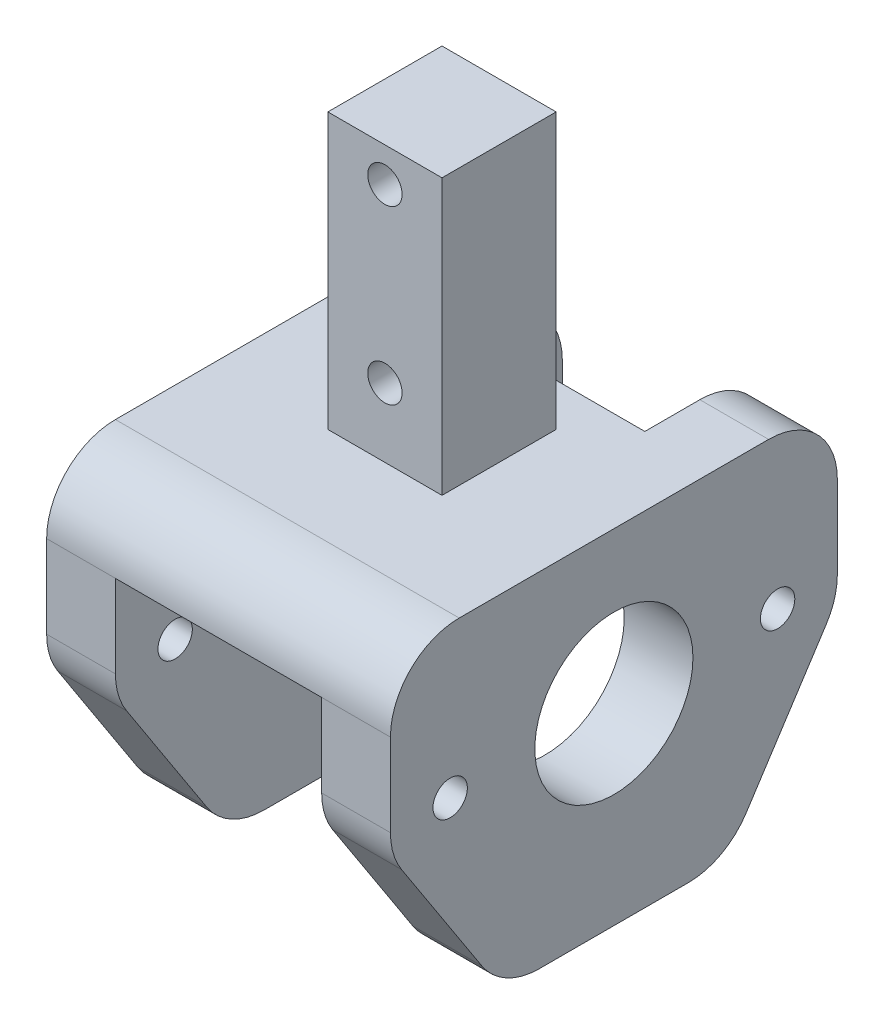
SolidWorks part; units mm, degrees
material "Nylon - impressão"
ref_plane "Plano frontal" through (0, 0, 0) normal (0, 0, 1) x (1, 0, 0)
ref_plane "Plano superior" through (0, 0, 0) normal (0, 1, 0) x (1, 0, 0)
ref_plane "Plano direito" through (0, 0, 0) normal (1, 0, 0) x (0, 0, -1)
sketch "Esboço1" plane through (0, 0, 0) normal (0, 1, 0) x (1, 0, 0)
  line L1 (-8.3, -8.3) -> (8.3, -8.3)
  line L2 (-8.3, -8.3) -> (-8.3, 8.3)
  line L3 (-8.3, 8.3) -> (8.3, 8.3)
  line L4 (8.3, -8.3) -> (8.3, 8.3)
  line L5 (-8.3, -8.3) -> (8.3, 8.3) construction
  line L6 (-8.3, 8.3) -> (8.3, -8.3) construction
  point P0 (0, 0)
  dimension "D1" = 16.6
extrude "Ressalto-extrusão1" add sketch "Esboço1" along normal blind 40
sketch "Esboço2" plane through (0, 0, 0) normal (0, -1, 0) x (1, 0, 0)
  line L1 (-25, -32.5) -> (25, -32.5)
  line L2 (-25, -32.5) -> (-25, 32.5)
  line L3 (-25, 32.5) -> (25, 32.5)
  line L4 (25, -32.5) -> (25, 32.5)
  line L5 (-25, -32.5) -> (25, 32.5) construction
  line L6 (-25, 32.5) -> (25, -32.5) construction
  point P0 (0, 0)
  dimension "D1" = 65
  dimension "D2" = 50
extrude "Ressalto-extrusão2" add sketch "Esboço2" along normal blind 50
sketch "Esboço3" plane through (0, 0, 32.5) normal (0, 0, 1) x (1, 0, 0)
  line L0 (25, -50) -> (-25, -50) construction
  line L1 (-15, -50) -> (15, -50)
  line L2 (-15, -50) -> (-15, -10)
  line L3 (-15, -10) -> (15, -10)
  line L4 (15, -50) -> (15, -10)
  line L5 (-25, -50) -> (-25, 0) construction
  line L6 (25, 0) -> (-25, 0) construction
  line L7 (25, -50) -> (25, 0) construction
  dimension "D1" = 10
  dimension "D2" = 10
  dimension "D3" = 10
extrude "Corte-extrusão1" cut sketch "Esboço3" against normal through all
sketch "Esboço4" plane through (25, 0, 0) normal (1, 0, 0) x (0, 0, -1)
  line L0 (32.5, -50) -> (-32.5, -50) construction
  line L1 (32.5, -50) -> (32.5, 0) construction
  circle A3 centre (0, -22) radius 11.5
  circle A10 centre (-23.8125, -22) radius 2.5
  circle A13 centre (23.8125, -22) radius 2.5
  circle A16 centre (0, -22) radius 23.8125 construction
  arc A17 (-9.4071, -1.4434) -> (-11.8406, -3.8769) centre (-11.9062, -1.3778) ccw [skipped]
  arc A18 (11.8464, -3.8771) -> (13.5071, -3.298) centre (11.9063, -1.3778) ccw [skipped]
  arc A20 (-11.8406, -45.1214) -> (-14.4054, -42.5566) centre (-11.9062, -42.6222) ccw [skipped]
  arc A21 (11.8345, -45.1212) -> (10.2346, -44.4811) centre (11.9063, -42.6222) ccw [skipped]
  point P21 (0, -22)
  point P22 (0, -22)
  dimension "D2" = 47.625
  dimension "D4" = 5
  dimension "D5" = 23
  dimension "D1" = 28
  dimension "D3" = 32.5
  dimension "D6" = 6
extrude "Corte-extrusão2" cut sketch "Esboço4" against normal through all
sketch "Esboço5" plane through (-25, 0, 0) normal (-1, 0, 0) x (0, 0, 1)
  line L0 (0, 0) -> (0, -9.2798) construction
  line L1 (32.5, 0) -> (-32.5, 0) construction
  line L3 (-14.5, -5) -> (-14.5, 0)
  line L4 (-14.5, 0) -> (-32.5, 0)
  line L5 (-32.5, 0) -> (-32.5, -5)
  line L6 (-32.5, -50) -> (-32.5, 0) construction
  line L7 (-32.5, -5) -> (-14.5, -5)
  point P5 (0, 0)
  line M5 (32.5, 0) -> (-32.5, 0)
  line M6 (-32.5, 0) -> (-32.5, -50)
  dimension "D1" = 18
  dimension "D2" = 5
extrude "Corte-extrusão3" cut sketch "Esboço5" against normal up to surface (10 mm away) contours L7 L3 M5 M6 region at (-25, -2.5, -23.5) up to face at (-15, -24.5, 23.8125)
sketch "Esboço8" plane through (-15, 0, 0) normal (-1, 0, 0) x (0, 0, 1)
  line L0 (-14.5, -5) -> (-14.5, 0) construction
  line L5 (-32.5, 0) -> (-14.5, 0)
  line L6 (-32.5, 0) -> (-32.5, -10)
  line L7 (-32.5, -10) -> (-14.5, -10)
  line L8 (-14.5, 0) -> (-14.5, -10)
  point P4 (0, 0)
  point P8 (0, 0)
  line M1 (-14.5, 0) -> (-32.5, 0)
  line M3 (-32.5, -5) -> (-14.5, -5)
  line M4 (-14.5, -5) -> (-14.5, 0)
  line M5 (-32.5, 0) -> (-32.5, -5)
chamfer "Chanfro1" distance 25 angle 33 4 edges at (-20, -50, -32.5) (-20, -50, 32.5) (20, -50, 32.5) (20, -50, -32.5) first distance on face at (-3, -23, -32.5) first distance on face at (0, -27.5, 32.5)
fillet "Filete2" radius 10 10 edges at (20, -25, -32.5) (20, -50, 16.2648) (20, -50, -16.2648) (20, -25, 32.5) (0, 0, 32.5) (-20, -50, -16.2648) (-20, -50, 16.2648) (-20, -25, 32.5) (-20, -25, -32.5) (-20, -5, -32.5)
extrude "Corte-extrusão5" cut sketch "Esboço8" against normal up to surface (30 mm away) contours M1 M5 M3 M4 | L8 L6 L7 M3 region at (-15, -2.5, -23.5) region at (-15, -7.5, -23.5) up to face at (15, -19.5, 23.8125)
fillet "Filete4" radius 10 1 edges at (20, 0, -32.5)
sketch "Esboço9" plane through (0, 0, 8.3) normal (0, 0, -1) x (-1, 0, 0)
  line L1 (-15, 0) -> (25, 0) construction
  circle A0 centre (0, 10) radius 2.5
  circle A1 centre (0, 35) radius 2.5
  point P4 (0, 0)
  point P8 (0, 0)
  point P9 (0, 0)
  point P10 (0, 0)
  dimension "D2" = 25
  dimension "D3" = 5
  dimension "D1" = 10
extrude "Corte-extrusão7" cut sketch "Esboço9" along normal through all contours A0 | A1
